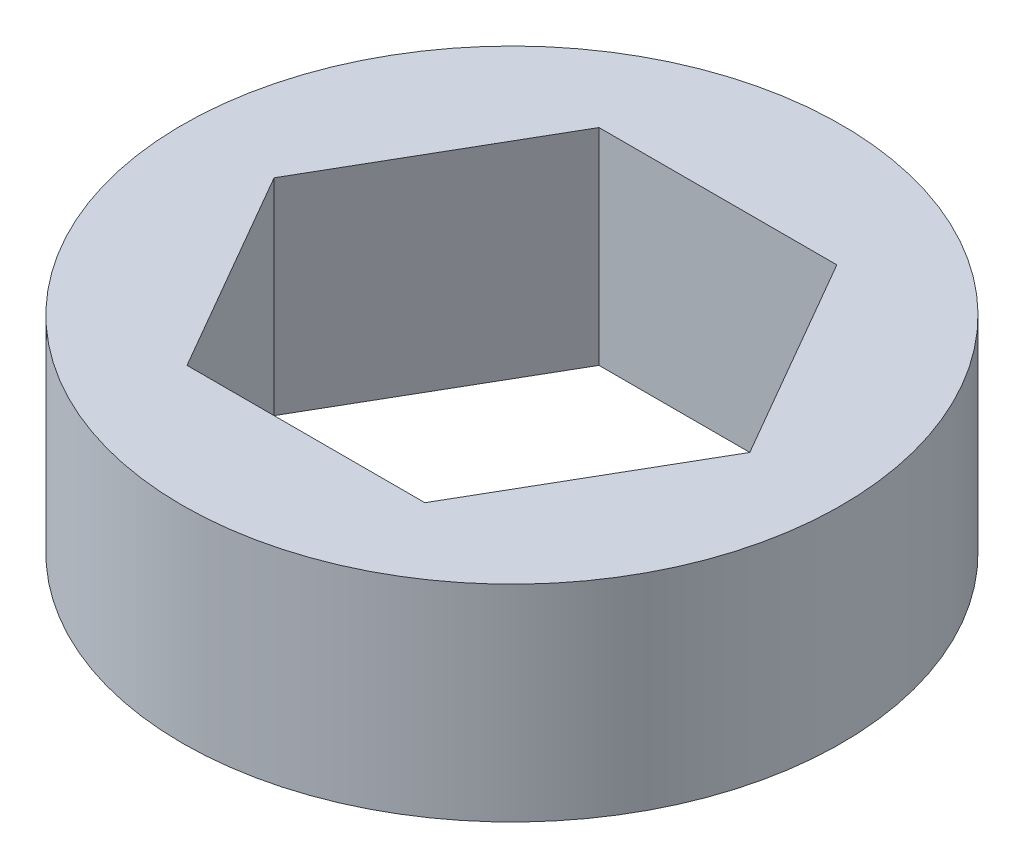
SolidWorks part; units mm, degrees
ref_plane "Front Plane" through (0, 0, 0) normal (0, 0, 1) x (1, 0, 0)
ref_plane "Top Plane" through (0, 0, 0) normal (0, 1, 0) x (1, 0, 0)
ref_plane "Right Plane" through (0, 0, 0) normal (1, 0, 0) x (0, 0, -1)
sketch "Sketch1" plane through (0, 0, 0) normal (0, 1, 0) x (1, 0, 0)
  line L1 (7.3323, 0) -> (3.6662, 6.35)
  line L2 (3.6662, 6.35) -> (-3.6662, 6.35)
  line L3 (-3.6662, 6.35) -> (-7.3323, 0)
  line L4 (-7.3323, 0) -> (-3.6662, -6.35)
  line L5 (-3.6662, -6.35) -> (3.6662, -6.35)
  line L6 (3.6662, -6.35) -> (7.3323, 0)
  circle A0 centre (0, 0) radius 6.35 construction
  circle A1 centre (0, 0) radius 10.16
  dimension "D2" = 20.32
  dimension "D1" = 12.7
extrude "Boss-Extrude1" add sketch "Sketch1" along normal blind 6.35
ref_axis "Axle" through (0, 17.7134, 0) along (0, -1, 0)
